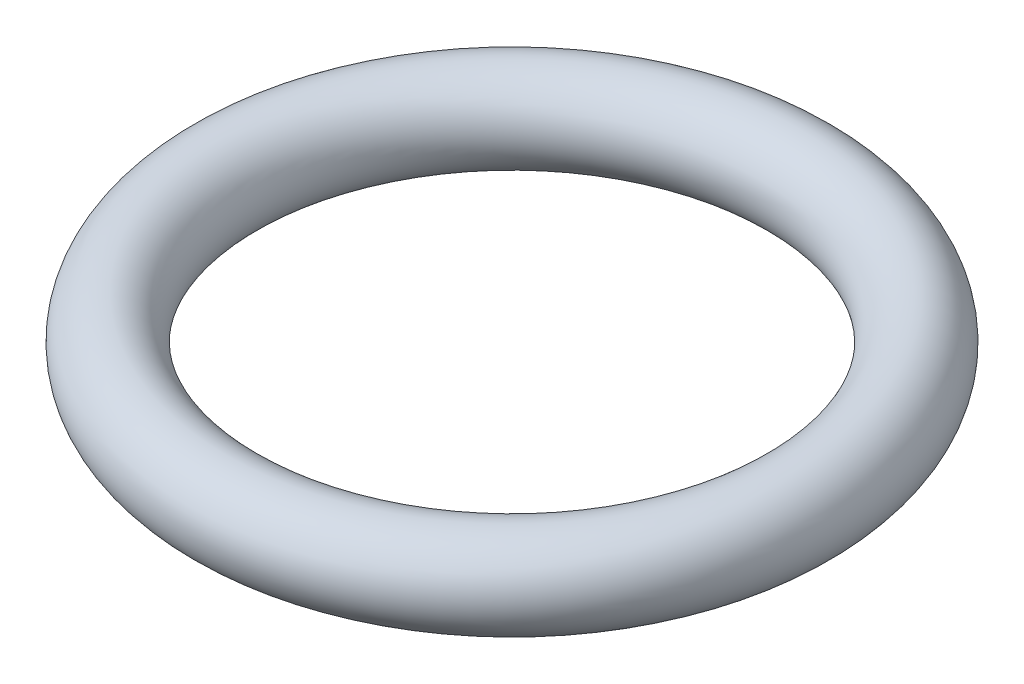
SolidWorks part; units mm, degrees
ref_plane "Front Plane" through (0, 0, 0) normal (0, 0, 1) x (1, 0, 0)
ref_plane "Top Plane" through (0, 0, 0) normal (0, 1, 0) x (1, 0, 0)
ref_plane "Right Plane" through (0, 0, 0) normal (1, 0, 0) x (0, 0, -1)
sketch "Sketch1" plane through (0, 0, 0) normal (0, 1, 0) x (1, 0, 0)
  circle A0 centre (0, 0) radius 5
  dimension "d1" = 10
sketch "Sketch2" plane through (0, 0, 0) normal (0, 0, 1) x (1, 0, 0)
  circle A0 centre (-5.9, 0) radius 0.9
  point P4 (-5, 0)
  dimension "d2" = 1.8
sweep "Sweep1" add profiles "Sketch2" path "Sketch1"
ref_axis "Axis1" through (0, 6.9817, 0) along (0, -1, 0)
